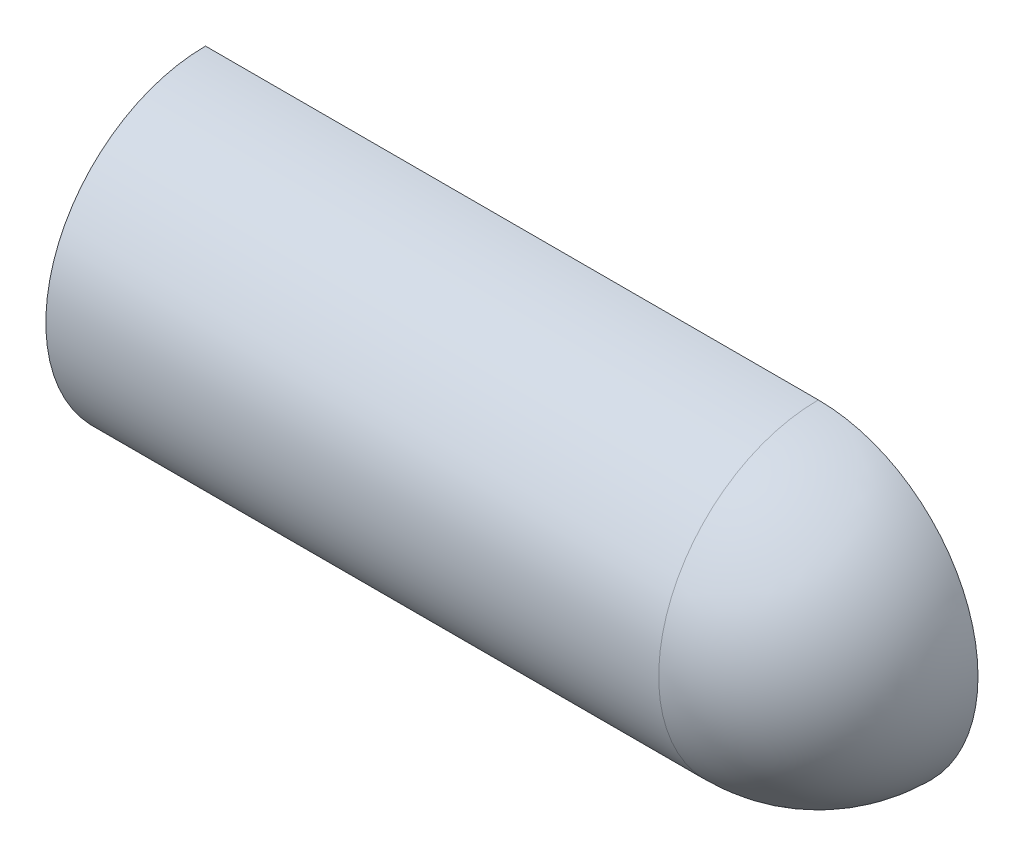
SolidWorks part; units mm, degrees
ref_plane "Front Plane" through (0, 0, 0) normal (0, 0, 1) x (1, 0, 0)
ref_plane "Top Plane" through (0, 0, 0) normal (0, 1, 0) x (1, 0, 0)
ref_plane "Right Plane" through (0, 0, 0) normal (1, 0, 0) x (0, 0, -1)
sketch "Sketch2" plane through (0, 0, 0) normal (0, 0, 1) x (1, 0, 0)
  line L0 (26, 0) -> (31, 0)
  line L2 (-119, 31) -> (0, 31)
  line L3 (-119, 31) -> (-119, 26)
  line L4 (0, 26) -> (-119, 26)
  arc A0 (12.8271, -28.2217) -> (-12.8271, 28.2217) centre (0, 0) ccw construction
  circle A1 centre (0, 0) radius 31 construction
  arc A3 (31, 0) -> (0, 31) centre (0, 0) ccw
  arc A4 (26, 0) -> (0, 26) centre (0, 0) ccw
revolve "Revolve1" add sketch "Sketch2" angle 180 about L0
